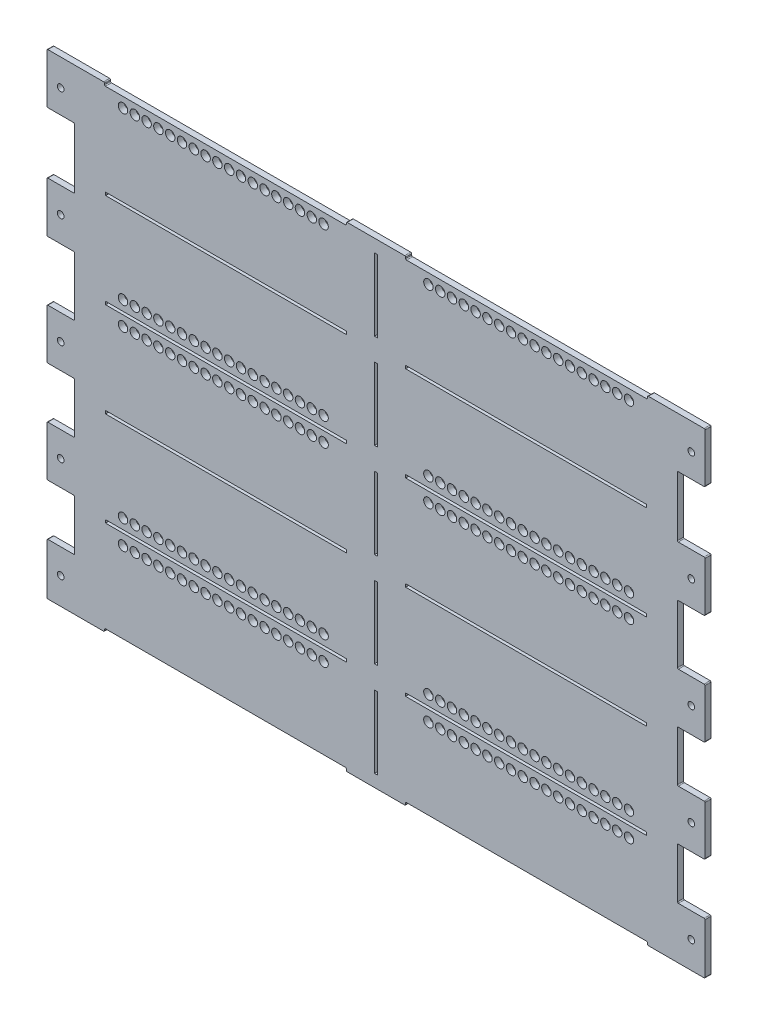
SolidWorks part; units mm, degrees
material "6061-T6 (SS)"
ref_plane "X-Y Datum" through (0, 0, 0) normal (0, 0, 1) x (1, 0, 0)
ref_plane "X-Z Datum" through (0, 0, 0) normal (0, 1, 0) x (1, 0, 0)
ref_plane "Y-Z Datum" through (0, 0, 0) normal (1, 0, 0) x (0, 0, -1)
sketch "Sketch1" plane through (0, 0, 0) normal (0, 0, 1) x (1, 0, 0)
  line L0 (-1.27, -1.27) -> (-1.27, 95.3084)
  line L1 (0, 0) -> (310.8274, 0)
  line L2 (0, 0) -> (0, 94.0384)
  line L3 (0, 94.0384) -> (310.8274, 94.0384)
  line L4 (310.8274, 0) -> (310.8274, 94.0384)
  line L5 (-1.27, 95.3084) -> (312.0974, 95.3084)
  line L6 (312.0974, -1.27) -> (312.0974, 95.3084)
  line L7 (-1.27, -1.27) -> (312.0974, -1.27)
  line L8 (-2.8575, 96.8959) -> (313.6849, 96.8959)
  line L9 (313.6849, -2.8575) -> (313.6849, 96.8959)
  line L10 (-2.8575, -2.8575) -> (313.6849, -2.8575)
  line L11 (-2.8575, -2.8575) -> (-2.8575, 96.8959)
  line L12 (0, 99.7534) -> (310.8274, 99.7534)
  line L13 (310.8274, 193.7918) -> (310.8274, 99.7534)
  line L14 (0, 193.7918) -> (310.8274, 193.7918)
  line L15 (0, 193.7918) -> (0, 99.7534)
  line L16 (-1.27, 195.0618) -> (312.0974, 195.0618)
  line L17 (312.0974, 195.0618) -> (312.0974, 98.4834)
  line L18 (-1.27, 98.4834) -> (312.0974, 98.4834)
  line L19 (-1.27, 195.0618) -> (-1.27, 98.4834)
  line L20 (-2.8575, 196.6493) -> (-2.8575, 96.8959)
  line L21 (-2.8575, 196.6493) -> (630.2273, 196.6493)
  line L23 (-2.8575, 296.4028) -> (630.2273, 296.4028)
  line L24 (-1.27, 198.2368) -> (-1.27, 294.8153)
  line L25 (-1.27, 294.8153) -> (312.0974, 294.8153)
  line L26 (312.0974, 198.2368) -> (312.0974, 294.8153)
  line L27 (-1.27, 198.2368) -> (312.0974, 198.2368)
  line L28 (0, 199.5068) -> (0, 293.5453)
  line L29 (0, 199.5068) -> (310.8274, 199.5068)
  line L30 (310.8274, 199.5068) -> (310.8274, 293.5453)
  line L31 (0, 293.5453) -> (310.8274, 293.5453)
  line L33 (313.6849, 96.8959) -> (313.6849, 196.6493)
  line L34 (-2.8575, 396.1562) -> (630.2273, 396.1562)
  line L35 (-1.27, 394.5687) -> (312.0974, 394.5687)
  line L36 (312.0974, 394.5687) -> (312.0974, 297.9903)
  line L37 (-1.27, 297.9903) -> (312.0974, 297.9903)
  line L38 (-1.27, 394.5687) -> (-1.27, 297.9903)
  line L39 (0, 393.2987) -> (310.8274, 393.2987)
  line L40 (310.8274, 393.2987) -> (310.8274, 299.2603)
  line L41 (0, 299.2603) -> (310.8274, 299.2603)
  line L42 (0, 393.2987) -> (0, 299.2603)
  line L43 (-2.8575, 296.4028) -> (-2.8575, 196.6493)
  line L44 (-2.8575, 495.9096) -> (-2.8575, 296.4028)
  line L45 (313.6849, 495.9096) -> (313.6849, 296.4028)
  line L46 (313.6849, 196.6493) -> (313.6849, 296.4028)
  line L47 (-2.8575, 495.9096) -> (630.2273, 495.9096)
  line L48 (-1.27, 397.7437) -> (-1.27, 494.3221)
  line L49 (-1.27, 494.3221) -> (312.0974, 494.3221)
  line L50 (312.0974, 397.7437) -> (312.0974, 494.3221)
  line L51 (-1.27, 397.7437) -> (312.0974, 397.7437)
  line L52 (0, 399.0137) -> (0, 493.0521)
  line L53 (0, 493.0521) -> (310.8274, 493.0521)
  line L54 (310.8274, 399.0137) -> (310.8274, 493.0521)
  line L55 (0, 399.0137) -> (310.8274, 399.0137)
  line L56 (313.6849, 595.663) -> (313.6849, 495.9096) construction
  line L57 (628.6398, 397.7437) -> (315.2724, 397.7437)
  line L58 (315.2724, 397.7437) -> (315.2724, 494.3221)
  line L59 (628.6398, 494.3221) -> (315.2724, 494.3221)
  line L60 (628.6398, 397.7437) -> (628.6398, 494.3221)
  line L61 (627.3698, 399.0137) -> (316.5424, 399.0137)
  line L62 (316.5424, 399.0137) -> (316.5424, 493.0521)
  line L63 (627.3698, 493.0521) -> (316.5424, 493.0521)
  line L64 (627.3698, 399.0137) -> (627.3698, 493.0521)
  line L65 (630.2273, 495.9096) -> (630.2273, 296.4028)
  line L66 (628.6398, 394.5687) -> (628.6398, 297.9903)
  line L67 (628.6398, 297.9903) -> (315.2724, 297.9903)
  line L68 (315.2724, 394.5687) -> (315.2724, 297.9903)
  line L69 (628.6398, 394.5687) -> (315.2724, 394.5687)
  line L70 (627.3698, 393.2987) -> (627.3698, 299.2603)
  line L71 (627.3698, 299.2603) -> (316.5424, 299.2603)
  line L72 (316.5424, 393.2987) -> (316.5424, 299.2603)
  line L73 (627.3698, 393.2987) -> (316.5424, 393.2987)
  line L74 (630.2273, 296.4028) -> (630.2273, 196.6493)
  line L75 (628.6398, 198.2368) -> (315.2724, 198.2368)
  line L76 (315.2724, 198.2368) -> (315.2724, 294.8153)
  line L77 (628.6398, 294.8153) -> (315.2724, 294.8153)
  line L78 (628.6398, 198.2368) -> (628.6398, 294.8153)
  line L79 (627.3698, 199.5068) -> (316.5424, 199.5068)
  line L80 (316.5424, 199.5068) -> (316.5424, 293.5453)
  line L81 (627.3698, 293.5453) -> (316.5424, 293.5453)
  line L82 (627.3698, 199.5068) -> (627.3698, 293.5453)
  line L83 (630.2273, 196.6493) -> (630.2273, 96.8959)
  line L84 (628.6398, 195.0618) -> (628.6398, 98.4834)
  line L85 (628.6398, 98.4834) -> (315.2724, 98.4834)
  line L86 (315.2724, 195.0618) -> (315.2724, 98.4834)
  line L87 (628.6398, 195.0618) -> (315.2724, 195.0618)
  line L88 (627.3698, 193.7918) -> (627.3698, 99.7534)
  line L89 (627.3698, 193.7918) -> (316.5424, 193.7918)
  line L90 (316.5424, 193.7918) -> (316.5424, 99.7534)
  line L91 (627.3698, 99.7534) -> (316.5424, 99.7534)
  line L92 (630.2273, -2.8575) -> (630.2273, 96.8959)
  line L93 (630.2273, -2.8575) -> (313.6849, -2.8575)
  line L94 (313.6849, -2.8575) -> (313.6849, 96.8959)
  line L95 (630.2273, 96.8959) -> (313.6849, 96.8959)
  line L96 (628.6398, -1.27) -> (315.2724, -1.27)
  line L97 (315.2724, -1.27) -> (315.2724, 95.3084)
  line L98 (628.6398, 95.3084) -> (315.2724, 95.3084)
  line L99 (628.6398, -1.27) -> (628.6398, 95.3084)
  line L100 (627.3698, 94.0384) -> (316.5424, 94.0384)
  line L101 (316.5424, 0) -> (316.5424, 94.0384)
  line L102 (627.3698, 0) -> (316.5424, 0)
  line L103 (627.3698, 0) -> (627.3698, 94.0384)
  point P56 (313.6849, 396.1562)
  dimension "D1" = 310.8274
  dimension "D2" = 94.0384
  dimension "D3" = 1.27
  dimension "D4" = 1.5875
sketch "Sketch2" plane through (0, 0, 0) normal (0, 0, 1) x (1, 0, 0)
  line L0 (0, 47.0192) -> (310.8274, 47.0192) construction
  line L1 (-1.27, -1.27) -> (628.6398, -1.27)
  line L2 (-1.27, -1.27) -> (-1.27, 494.3221)
  line L3 (-1.27, 494.3221) -> (628.6398, 494.3221)
  line L4 (628.6398, -1.27) -> (628.6398, 494.3221)
  line L5 (0, 0) -> (0, 94.0384) construction
  line L6 (310.8274, 0) -> (310.8274, 94.0384) construction
  line L7 (155.4137, 47.0192) -> (155.4137, 163.8162) construction
  line L8 (-2.8575, 96.8959) -> (313.6849, 96.8959) construction
  line L9 (28.4137, 95.3084) -> (282.4137, 95.3084)
  line L10 (28.4137, 95.3084) -> (28.4137, 98.4834)
  line L11 (28.4137, 98.4834) -> (282.4137, 98.4834)
  line L12 (282.4137, 95.3084) -> (282.4137, 98.4834)
  line L13 (28.4137, 95.3084) -> (282.4137, 98.4834) construction
  line L14 (28.4137, 98.4834) -> (282.4137, 95.3084) construction
  line L15 (-1.27, 98.4834) -> (312.0974, 98.4834) construction
  line L16 (-2.8575, 196.6493) -> (630.2273, 196.6493) construction
  line L17 (28.4137, 195.0618) -> (282.4137, 195.0618)
  line L18 (28.4137, 195.0618) -> (28.4137, 198.2368)
  line L19 (28.4137, 198.2368) -> (282.4137, 198.2368)
  line L20 (282.4137, 195.0618) -> (282.4137, 198.2368)
  line L21 (28.4137, 195.0618) -> (282.4137, 198.2368) construction
  line L22 (28.4137, 198.2368) -> (282.4137, 195.0618) construction
  line L23 (-1.27, 198.2368) -> (312.0974, 198.2368) construction
  line L24 (315.2724, -1.27) -> (315.2724, 95.3084) construction
  line L25 (-2.8575, 296.4028) -> (630.2273, 296.4028) construction
  line L26 (28.4137, 294.8153) -> (282.4137, 294.8153)
  line L27 (28.4137, 294.8153) -> (28.4137, 297.9903)
  line L28 (28.4137, 297.9903) -> (282.4137, 297.9903)
  line L29 (282.4137, 294.8153) -> (282.4137, 297.9903)
  line L30 (28.4137, 294.8153) -> (282.4137, 297.9903) construction
  line L31 (28.4137, 297.9903) -> (282.4137, 294.8153) construction
  line L32 (-1.27, 297.9903) -> (312.0974, 297.9903) construction
  line L33 (-2.8575, 396.1562) -> (630.2273, 396.1562) construction
  line L34 (28.4137, 394.5687) -> (282.4137, 394.5687)
  line L35 (28.4137, 394.5687) -> (28.4137, 397.7437)
  line L36 (28.4137, 397.7437) -> (282.4137, 397.7437)
  line L37 (282.4137, 394.5687) -> (282.4137, 397.7437)
  line L38 (28.4137, 394.5687) -> (282.4137, 397.7437) construction
  line L39 (28.4137, 397.7437) -> (282.4137, 394.5687) construction
  line L40 (-1.27, 397.7437) -> (312.0974, 397.7437) construction
  line L41 (313.6849, 604.3732) -> (313.6849, -52.4712) construction
  line L42 (598.9561, 98.4834) -> (344.9561, 98.4834)
  line L43 (344.9561, 95.3084) -> (344.9561, 98.4834)
  line L44 (598.9561, 95.3084) -> (344.9561, 95.3084)
  line L45 (598.9561, 95.3084) -> (598.9561, 98.4834)
  line L46 (598.9561, 198.2368) -> (344.9561, 198.2368)
  line L47 (344.9561, 195.0618) -> (344.9561, 198.2368)
  line L48 (598.9561, 195.0618) -> (344.9561, 195.0618)
  line L49 (598.9561, 195.0618) -> (598.9561, 198.2368)
  line L50 (598.9561, 397.7437) -> (344.9561, 397.7437)
  line L51 (344.9561, 394.5687) -> (344.9561, 397.7437)
  line L52 (598.9561, 394.5687) -> (344.9561, 394.5687)
  line L53 (598.9561, 394.5687) -> (598.9561, 397.7437)
  line L54 (598.9561, 297.9903) -> (344.9561, 297.9903)
  line L55 (344.9561, 294.8153) -> (344.9561, 297.9903)
  line L56 (598.9561, 294.8153) -> (344.9561, 294.8153)
  line L57 (598.9561, 294.8153) -> (598.9561, 297.9903)
  line L58 (312.0974, 8.5255) -> (315.2724, 8.5255)
  line L59 (312.0974, 8.5255) -> (312.0974, 84.7255)
  line L60 (312.0974, 84.7255) -> (315.2724, 84.7255)
  line L61 (315.2724, 8.5255) -> (315.2724, 84.7255)
  line L62 (312.0974, 8.5255) -> (315.2724, 84.7255) construction
  line L63 (312.0974, 84.7255) -> (315.2724, 8.5255) construction
  line L64 (310.8274, 193.7918) -> (310.8274, 99.7534) construction
  line L65 (310.8274, 146.7726) -> (337.6409, 146.7726) construction
  line L66 (315.2724, 195.0618) -> (315.2724, 98.4834) construction
  line L67 (312.0974, 108.6726) -> (315.2724, 108.6726)
  line L68 (312.0974, 108.6726) -> (312.0974, 184.8726)
  line L69 (312.0974, 184.8726) -> (315.2724, 184.8726)
  line L70 (315.2724, 108.6726) -> (315.2724, 184.8726)
  line L71 (312.0974, 108.6726) -> (315.2724, 184.8726) construction
  line L72 (312.0974, 184.8726) -> (315.2724, 108.6726) construction
  line L73 (310.8274, 293.5453) -> (310.8274, 199.5068) construction
  line L74 (310.8274, 246.5261) -> (343.3258, 246.5261) construction
  line L75 (315.2724, 198.2368) -> (315.2724, 294.8153) construction
  line L76 (312.0974, 208.4261) -> (315.2724, 208.4261)
  line L77 (312.0974, 208.4261) -> (312.0974, 284.6261)
  line L78 (312.0974, 284.6261) -> (315.2724, 284.6261)
  line L79 (315.2724, 208.4261) -> (315.2724, 284.6261)
  line L80 (312.0974, 208.4261) -> (315.2724, 284.6261) construction
  line L81 (312.0974, 284.6261) -> (315.2724, 208.4261) construction
  line L82 (310.8274, 299.2603) -> (310.8274, 393.2987) construction
  line L83 (310.8274, 493.0521) -> (310.8274, 399.0137) construction
  line L84 (310.8274, 346.2795) -> (351.536, 346.2795) construction
  line L85 (310.8274, 446.0329) -> (345.4409, 446.0329) construction
  line L86 (315.2724, 394.5687) -> (315.2724, 297.9903) construction
  line L87 (312.0974, 308.1795) -> (315.2724, 308.1795)
  line L88 (312.0974, 308.1795) -> (312.0974, 384.3795)
  line L89 (312.0974, 384.3795) -> (315.2724, 384.3795)
  line L90 (315.2724, 308.1795) -> (315.2724, 384.3795)
  line L91 (312.0974, 308.1795) -> (315.2724, 384.3795) construction
  line L92 (312.0974, 384.3795) -> (315.2724, 308.1795) construction
  line L93 (315.2724, 397.7437) -> (315.2724, 494.3221) construction
  line L94 (312.0974, 407.9329) -> (315.2724, 407.9329)
  line L95 (312.0974, 407.9329) -> (312.0974, 484.1329)
  line L96 (312.0974, 484.1329) -> (315.2724, 484.1329)
  line L97 (315.2724, 407.9329) -> (315.2724, 484.1329)
  line L98 (312.0974, 407.9329) -> (315.2724, 484.1329) construction
  line L99 (312.0974, 484.1329) -> (315.2724, 407.9329) construction
  point P13 (155.4137, 96.8959)
  point P23 (155.4137, 196.6493)
  point P32 (155.4137, 296.4028)
  point P41 (155.4137, 396.1562)
  point P52 (313.6849, 46.6255)
  point P80 (313.6849, 146.7726)
  point P93 (313.6849, 246.526)
  point P114 (313.6849, 346.2795)
  point P122 (313.6849, 446.0329)
  dimension "D1" = 254
  dimension "D2" = 254
  dimension "D3" = 254
  dimension "D4" = 254
  dimension "D5" = 76.2
  dimension "D6" = 76.2
  dimension "D7" = 3.175
  dimension "D8" = 99.7534
  dimension "D9" = 76.2
  dimension "D10" = 99.7534
  dimension "D11" = 99.7534
  dimension "D12" = 99.7534
  dimension "D13" = 76.2
  dimension "D14" = 76.2
extrude "Boss-Extrude1" add sketch "Sketch2" along normal blind 6.35
sketch "Sketch4" plane through (0, 0, 6.35) normal (0, 0, 1) x (1, 0, 0)
  line L0 (313.6849, 484.1329) -> (313.6849, 506.6663) construction
  line L1 (-1.27, -1.27) -> (27.315, -1.27)
  line L2 (-1.27, -1.27) -> (-1.27, -4.445)
  line L3 (-1.27, -4.445) -> (27.315, -4.445)
  line L4 (628.6398, -1.27) -> (628.6398, -4.445)
  line L6 (27.315, -1.27) -> (27.315, -4.445)
  line L8 (282.4137, -1.27) -> (282.4137, -4.445)
  line L9 (600.0548, -1.27) -> (628.6398, -1.27)
  line L11 (344.9561, -1.27) -> (344.9561, -4.445)
  line L13 (600.0548, -1.27) -> (600.0548, -4.445)
  line L14 (600.0548, -4.445) -> (628.6398, -4.445)
  line L15 (282.4137, -1.27) -> (344.9561, -1.27)
  line L16 (282.4137, -4.445) -> (344.9561, -4.445)
  line L17 (-1.27, 246.526) -> (668.9088, 246.526) construction
  line L18 (-1.27, 494.3221) -> (-1.27, -1.27) construction
  line L19 (600.0548, 494.3221) -> (628.6398, 494.3221)
  line L20 (600.0548, 494.3221) -> (600.0548, 497.4971)
  line L21 (600.0548, 497.4971) -> (628.6398, 497.4971)
  line L22 (628.6398, 494.3221) -> (628.6398, 497.4971)
  line L23 (282.4137, 494.3221) -> (344.9561, 494.3221)
  line L24 (344.9561, 494.3221) -> (344.9561, 497.4971)
  line L25 (282.4137, 497.4971) -> (344.9561, 497.4971)
  line L26 (282.4137, 494.3221) -> (282.4137, 497.4971)
  line L27 (-1.27, 494.3221) -> (27.315, 494.3221)
  line L28 (-1.27, 494.3221) -> (-1.27, 497.4971)
  line L29 (-1.27, 497.4971) -> (27.315, 497.4971)
  line L30 (27.315, 494.3221) -> (27.315, 497.4971)
extrude "Boss-Extrude2" add sketch "Sketch4" against normal through all contours L3 L0 L1 L8 L6 L2 | L0 L3 L4 L1 L13 L11 | L13 L14 L4 L9 | L26 L23 L24 L25 | L19 L22 L21 L20 | L8 L16 L11 L15 | L4 L14 L13 L9 | L29 L30 L27 L28 region at (13.0225, -2.8575, 6.35) region at (614.3473, -2.8575, 6.35) region at (614.3473, 495.9096, 6.35) region at (313.6849, 495.9096, 6.35)
sketch "Sketch5" plane through (0, 0, 6.35) normal (0, 0, 1) x (1, 0, 0)
  line L0 (313.6849, 646.2482) -> (313.6849, -137.2183) construction
  line L9 (628.6398, 526.4531) -> (469.3361, 526.4531) construction
  line L18 (469.3361, 510.1236) -> (469.3361, 526.4531) construction
  line L19 (-1.27, 494.3221) -> (628.6398, 494.3221) construction
  line L20 (-1.27, 494.3221) -> (-1.27, 497.4971) construction
  line L21 (158.0337, 510.1236) -> (469.3361, 510.1236) construction
  line L22 (628.6398, 494.3221) -> (628.6398, 497.4971) construction
  line L24 (-1.27, 497.4971) -> (-1.27, 526.4531) construction
  line L25 (-1.27, 526.4531) -> (158.0337, 526.4531) construction
  line L26 (158.0337, 510.1236) -> (158.0337, 526.4531) construction
  line L28 (628.6398, 497.4971) -> (628.6398, 526.4531) construction
  line L29 (-1.27, 244.9386) -> (684.2814, 244.9386) construction
  line L30 (-33.401, 494.3221) -> (-33.401, 497.4971)
  line L41 (628.6398, 494.3221) -> (628.6398, -4.445)
  line L43 (660.7708, 494.3221) -> (660.7708, -4.445)
  line L44 (628.6398, -4.445) -> (660.7708, -4.445)
  line L45 (-1.27, -4.445) -> (-33.401, -4.445)
  line L46 (-33.401, 494.3221) -> (-33.401, -4.445)
  line L48 (-1.27, 494.3221) -> (-1.27, -4.445)
  line L49 (-33.401, 497.4971) -> (-1.27, 497.4971)
  line L50 (-1.27, 497.4971) -> (-1.27, 494.3221)
  line L51 (628.6398, 497.4971) -> (660.7708, 497.4971)
  line L52 (660.7708, 497.4971) -> (660.7708, 494.3221)
  line L53 (628.6398, 497.4971) -> (628.6398, 494.3221)
extrude "Boss-Extrude3" add sketch "Sketch5" against normal through all
sketch "Sketch6" plane through (0, 0, 6.35) normal (0, 0, 1) x (1, 0, 0)
  line L0 (-33.401, 497.4971) -> (-33.401, -4.445) construction
  line L1 (-18.923, 237.4868) -> (-18.923, 23.73) construction
  line L2 (-58.003, 491.1471) -> (-58.003, 0) construction
  line L4 (-33.401, -4.445) -> (27.315, -4.445) construction
  line L5 (-18.923, 486.1471) -> (-18.923, 469.3221) construction
  line L6 (-18.923, 469.3221) -> (-18.923, 237.4868) construction
  line L7 (313.6849, 494.3221) -> (313.6849, 517.9624) construction
  line L8 (-33.401, 497.4971) -> (27.315, 497.4971) construction
  circle A0 centre (-18.923, 23.73) radius 7.1006 construction
  circle A1 centre (-18.923, 469.3221) radius 7.1006 construction
  circle A2 centre (-18.923, 237.4868) radius 7.1006 construction
  circle A3 centre (-18.923, 130.6084) radius 7.1006 construction
  circle A4 centre (-18.923, 353.4045) radius 7.1006 construction
  point P17 (-18.923, 469.3221)
  point P18 (-18.923, 23.73)
  point P21 (-18.923, 237.4868)
  point P22 (-18.923, 130.6084)
  point P25 (-18.923, 353.4045)
  point P26 (646.2928, 23.73)
  point P27 (646.2928, 130.6084)
  point P28 (646.2928, 237.4868)
  point P30 (646.2928, 353.4045)
  point P31 (646.2928, 469.3221)
  dimension "D1" = 14.478
  dimension "D2" = 28.175
  dimension "D3" = 28.175
hole_wizard "M6 Clearance Hole1" positions "Sketch11" profile "Sketch10" hole size "M6" standard "ANSI Metric" end condition through all
sketch "Sketch11" plane through (0, 0, 6.35) normal (0, 0, 1) x (1, 0, 0)
  line L0 (-18.923, 237.4868) -> (-18.923, 23.73) construction
  point P0 (-18.923, 469.3221)
  point P3 (-18.923, 353.4045)
  point P6 (-18.923, 237.4868)
  point P9 (-18.923, 130.6084)
  point P13 (-18.923, 23.73)
  point P16 (646.2928, 23.73)
  point P19 (646.2928, 130.6084)
  point P22 (646.2928, 237.4868)
  point P25 (646.2928, 353.4045)
  point P28 (646.2928, 469.3221)
sketch "Sketch10" plane through (-18.923, 469.3221, 6.35) normal (1, 0, 0) x (0, -1, 0)
  line L0 (0, 0) -> (0, 6.35)
  line L1 (0, 6.35) -> (3.5, 6.35)
  line L2 (3.5, 6.35) -> (3.5, 0)
  line L5 (3.5, 0) -> (0, 0)
  line L11 (0, -6.35) -> (0, 107.95) construction
  dimension "Thru Hole Dia." = 7
  dimension "Thru Hole Depth" = 6.35
sketch "Sketch13" plane through (0, 0, 6.35) normal (0, 0, 1) x (1, 0, 0)
  line L0 (-33.401, 444.3971) -> (-4.3178, 444.3971)
  line L1 (-33.401, 444.3971) -> (-33.401, 380.1105)
  line L2 (-33.401, 380.1105) -> (-4.3178, 380.1105)
  line L3 (-4.3178, 444.3971) -> (-4.3178, 380.1105)
  line L4 (-33.401, 326.6985) -> (-4.3178, 326.6985)
  line L5 (-33.401, 326.6985) -> (-33.401, 263.9908)
  line L6 (-33.401, 263.9908) -> (-4.3178, 263.9908)
  line L7 (-4.3178, 326.6985) -> (-4.3178, 263.9908)
  line L8 (-33.401, 210.9829) -> (-4.3178, 210.9829)
  line L9 (-33.401, 210.9829) -> (-33.401, 157.1261)
  line L10 (-33.401, 157.1261) -> (-4.3178, 157.1261)
  line L11 (-4.3178, 210.9829) -> (-4.3178, 157.1261)
  line L12 (-33.401, 104.0907) -> (-4.3178, 104.0907)
  line L13 (-33.401, 104.0907) -> (-33.401, 50.0595)
  line L14 (-33.401, 50.0595) -> (-4.3178, 50.0595)
  line L15 (-4.3178, 104.0907) -> (-4.3178, 50.0595)
  line L32 (-33.5282, 492.6971) -> (660.7708, 492.6971) construction
  line L33 (-33.5282, 492.6971) -> (-33.5282, -1.3734) construction
  line L34 (-33.5282, -1.3734) -> (660.7708, -1.3734) construction
  line L36 (313.6849, 84.7255) -> (313.6849, 116.6988) construction
  line L37 (-33.401, 497.4971) -> (-4.445, 497.4971) construction
  line L38 (-33.401, 497.4971) -> (-33.401, 418.9959) construction
  line L39 (-33.401, 418.9959) -> (-4.445, 418.9959) construction
  line L40 (-4.445, 497.4971) -> (-4.445, 418.9959) construction
  line L41 (-4.3178, 326.6985) -> (-33.5282, 326.6985) construction
  line L42 (-4.3178, 326.6985) -> (-4.3178, 380.1105) construction
  line L43 (-4.3178, 380.1105) -> (-33.5282, 380.1105) construction
  line L44 (-33.5282, 326.6985) -> (-33.5282, 380.1105) construction
  line L45 (-4.3178, 326.6985) -> (-33.5282, 380.1105) construction
  line L46 (-4.3178, 380.1105) -> (-33.5282, 326.6985) construction
  line L47 (-33.5282, 210.9829) -> (-4.3178, 210.9829) construction
  line L48 (-33.5282, 210.9829) -> (-33.5282, 263.9908) construction
  line L49 (-33.5282, 263.9908) -> (-4.3178, 263.9908) construction
  line L50 (-4.3178, 210.9829) -> (-4.3178, 263.9908) construction
  line L51 (-33.5282, 210.9829) -> (-4.3178, 263.9908) construction
  line L52 (-33.5282, 263.9908) -> (-4.3178, 210.9829) construction
  line L53 (-33.5282, 104.0907) -> (-4.3178, 104.0907) construction
  line L54 (-33.5282, 104.0907) -> (-33.5282, 157.1261) construction
  line L55 (-33.5282, 157.1261) -> (-4.3178, 157.1261) construction
  line L56 (-4.3178, 104.0907) -> (-4.3178, 157.1261) construction
  line L57 (-33.5282, 104.0907) -> (-4.3178, 157.1261) construction
  line L58 (-33.5282, 157.1261) -> (-4.3178, 104.0907) construction
  line L59 (-33.5282, -2.5995) -> (-4.3178, -2.5995) construction
  line L60 (-33.5282, -2.5995) -> (-33.5282, 50.0595) construction
  line L61 (-33.5282, 50.0595) -> (-4.3178, 50.0595) construction
  line L62 (-4.3178, -2.5995) -> (-4.3178, 50.0595) construction
  line L63 (-33.5282, -2.5995) -> (-4.3178, 50.0595) construction
  line L64 (-33.5282, 50.0595) -> (-4.3178, -2.5995) construction
  line L66 (660.7708, 104.0907) -> (660.7708, 50.0595)
  line L67 (660.7708, 50.0595) -> (631.6876, 50.0595)
  line L68 (631.6876, 104.0907) -> (631.6876, 50.0595)
  line L69 (660.7708, 104.0907) -> (631.6876, 104.0907)
  line L70 (660.7708, 210.9829) -> (660.7708, 157.1261)
  line L71 (660.7708, 157.1261) -> (631.6876, 157.1261)
  line L72 (631.6876, 210.9829) -> (631.6876, 157.1261)
  line L73 (660.7708, 210.9829) -> (631.6876, 210.9829)
  line L74 (660.7708, 326.6985) -> (660.7708, 263.9908)
  line L75 (660.7708, 263.9908) -> (631.6876, 263.9908)
  line L76 (631.6876, 326.6985) -> (631.6876, 263.9908)
  line L77 (660.7708, 326.6985) -> (631.6876, 326.6985)
  line L78 (660.7708, 444.3971) -> (660.7708, 380.1105)
  line L79 (660.7708, 380.1105) -> (631.6876, 380.1105)
  line L80 (631.6876, 444.3971) -> (631.6876, 380.1105)
  line L81 (660.7708, 444.3971) -> (631.6876, 444.3971)
  point P1 (-18.923, 237.4868)
  point P5 (-18.923, 130.6084)
  point P9 (-18.923, 23.73)
  point P41 (-18.923, 353.4045)
extrude "Cut-Extrude1" cut sketch "Sketch13" against normal through all
sketch "Sketch15" plane through (0, 0, 0) normal (0, 0, 1) x (1, 0, 0)
  line L0 (28.4137, 397.7437) -> (282.4137, 397.7437) construction
  line L1 (28.4137, 394.5687) -> (279.5273, 394.5687) construction
  line L2 (28.4137, 394.5687) -> (282.4137, 394.5687) construction
  line L7 (-1.27, 491.1471) -> (628.6398, 491.1471) construction
  line L8 (-1.27, 491.1471) -> (-1.27, 0.1766) construction
  line L9 (-1.27, 0.1766) -> (628.6398, 0.1766) construction
  line L10 (628.6398, 491.1471) -> (628.6398, 0.1766) construction
  line L11 (28.4137, 198.2368) -> (282.4137, 198.2368) construction
  line L12 (282.4137, 195.0618) -> (28.4137, 195.0618) construction
  line L13 (27.315, -1.27) -> (282.4137, -1.27) construction
  line L14 (313.6849, 484.1329) -> (313.6849, 511.0054) construction
  line L15 (312.0974, 446.0329) -> (-60.7128, 446.0329) construction
  line L16 (312.0974, 484.1329) -> (312.0974, 407.9329) construction
  line L17 (312.0974, 346.2795) -> (183.7106, 346.2795) construction
  line L18 (312.0974, 46.6255) -> (242.3736, 46.6255) construction
  line L19 (312.0974, 246.5261) -> (190.4752, 246.5261) construction
  line L21 (312.0974, 146.7726) -> (233.4946, 146.7726) construction
  line L22 (312.0974, 184.8726) -> (312.0974, 108.6726) construction
  circle A306 centre (580.5653, 483.6541) radius 5
  circle A307 centre (568.1193, 483.6541) radius 5
  circle A308 centre (555.6733, 483.6541) radius 5
  circle A309 centre (543.2273, 483.6541) radius 5
  circle A310 centre (530.7813, 483.6541) radius 5
  circle A311 centre (518.3353, 483.6541) radius 5
  circle A312 centre (505.8893, 483.6541) radius 5
  circle A313 centre (493.4433, 483.6541) radius 5
  circle A314 centre (480.9973, 483.6541) radius 5
  circle A315 centre (468.5513, 483.6541) radius 5
  circle A316 centre (456.1053, 483.6541) radius 5
  circle A317 centre (443.6593, 483.6541) radius 5
  circle A318 centre (431.2133, 483.6541) radius 5
  circle A319 centre (418.7673, 483.6541) radius 5
  circle A320 centre (406.3213, 483.6541) radius 5
  circle A321 centre (393.8753, 483.6541) radius 5
  circle A322 centre (381.4293, 483.6541) radius 5
  circle A323 centre (368.9833, 483.6541) radius 5
  circle A324 centre (258.3866, 483.6541) radius 5
  circle A325 centre (245.9406, 483.6541) radius 5
  circle A326 centre (233.4946, 483.6541) radius 5
  circle A327 centre (221.0486, 483.6541) radius 5
  circle A328 centre (208.6026, 483.6541) radius 5
  circle A329 centre (196.1566, 483.6541) radius 5
  circle A330 centre (183.7106, 483.6541) radius 5
  circle A331 centre (171.2646, 483.6541) radius 5
  circle A332 centre (158.8186, 483.6541) radius 5
  circle A333 centre (146.3726, 483.6541) radius 5
  circle A334 centre (133.9266, 483.6541) radius 5
  circle A335 centre (121.4806, 483.6541) radius 5
  circle A336 centre (109.0346, 483.6541) radius 5
  circle A337 centre (96.5886, 483.6541) radius 5
  circle A338 centre (84.1426, 483.6541) radius 5
  circle A339 centre (71.6966, 483.6541) radius 5
  circle A340 centre (59.2506, 483.6541) radius 5
  circle A341 centre (46.8046, 483.6541) radius 5
  circle A359 centre (580.5653, 308.6583) radius 5
  circle A360 centre (568.1193, 308.6583) radius 5
  circle A361 centre (555.6733, 308.6583) radius 5
  circle A362 centre (543.2273, 308.6583) radius 5
  circle A363 centre (530.7813, 308.6583) radius 5
  circle A364 centre (518.3353, 308.6583) radius 5
  circle A365 centre (505.8893, 308.6583) radius 5
  circle A366 centre (493.4433, 308.6583) radius 5
  circle A367 centre (480.9973, 308.6583) radius 5
  circle A368 centre (468.5513, 308.6583) radius 5
  circle A369 centre (456.1053, 308.6583) radius 5
  circle A370 centre (443.6593, 308.6583) radius 5
  circle A371 centre (431.2133, 308.6583) radius 5
  circle A372 centre (418.7673, 308.6583) radius 5
  circle A373 centre (406.3213, 308.6583) radius 5
  circle A374 centre (393.8753, 308.6583) radius 5
  circle A375 centre (381.4293, 308.6583) radius 5
  circle A376 centre (368.9833, 308.6583) radius 5
  circle A377 centre (258.3866, 308.6583) radius 5
  circle A378 centre (245.9406, 308.6583) radius 5
  circle A379 centre (233.4946, 308.6583) radius 5
  circle A380 centre (221.0486, 308.6583) radius 5
  circle A381 centre (208.6026, 308.6583) radius 5
  circle A382 centre (196.1566, 308.6583) radius 5
  circle A383 centre (183.7106, 308.6583) radius 5
  circle A384 centre (171.2646, 308.6583) radius 5
  circle A385 centre (158.8186, 308.6583) radius 5
  circle A386 centre (146.3726, 308.6583) radius 5
  circle A387 centre (133.9266, 308.6583) radius 5
  circle A388 centre (121.4806, 308.6583) radius 5
  circle A389 centre (109.0346, 308.6583) radius 5
  circle A390 centre (96.5886, 308.6583) radius 5
  circle A391 centre (84.1426, 308.6583) radius 5
  circle A392 centre (71.6966, 308.6583) radius 5
  circle A393 centre (59.2506, 308.6583) radius 5
  circle A394 centre (46.8046, 308.6583) radius 5
  circle A412 centre (580.5653, 284.1473) radius 5
  circle A413 centre (568.1193, 284.1473) radius 5
  circle A414 centre (555.6733, 284.1473) radius 5
  circle A415 centre (543.2273, 284.1473) radius 5
  circle A416 centre (530.7813, 284.1473) radius 5
  circle A417 centre (518.3353, 284.1473) radius 5
  circle A418 centre (505.8893, 284.1473) radius 5
  circle A419 centre (493.4433, 284.1473) radius 5
  circle A420 centre (480.9973, 284.1473) radius 5
  circle A421 centre (468.5513, 284.1473) radius 5
  circle A422 centre (456.1053, 284.1473) radius 5
  circle A423 centre (443.6593, 284.1473) radius 5
  circle A424 centre (431.2133, 284.1473) radius 5
  circle A425 centre (418.7673, 284.1473) radius 5
  circle A426 centre (406.3213, 284.1473) radius 5
  circle A427 centre (393.8753, 284.1473) radius 5
  circle A428 centre (381.4293, 284.1473) radius 5
  circle A429 centre (368.9833, 284.1473) radius 5
  circle A430 centre (258.3866, 284.1473) radius 5
  circle A431 centre (245.9406, 284.1473) radius 5
  circle A432 centre (233.4946, 284.1473) radius 5
  circle A433 centre (221.0486, 284.1473) radius 5
  circle A434 centre (208.6026, 284.1473) radius 5
  circle A435 centre (196.1566, 284.1473) radius 5
  circle A436 centre (183.7106, 284.1473) radius 5
  circle A437 centre (171.2646, 284.1473) radius 5
  circle A438 centre (158.8186, 284.1473) radius 5
  circle A439 centre (146.3726, 284.1473) radius 5
  circle A440 centre (133.9266, 284.1473) radius 5
  circle A441 centre (121.4806, 284.1473) radius 5
  circle A442 centre (109.0346, 284.1473) radius 5
  circle A443 centre (96.5886, 284.1473) radius 5
  circle A444 centre (84.1426, 284.1473) radius 5
  circle A445 centre (71.6966, 284.1473) radius 5
  circle A446 centre (59.2506, 284.1473) radius 5
  circle A447 centre (46.8046, 284.1473) radius 5
  circle A465 centre (580.5653, 109.1514) radius 5
  circle A466 centre (568.1193, 109.1514) radius 5
  circle A467 centre (555.6733, 109.1514) radius 5
  circle A468 centre (543.2273, 109.1514) radius 5
  circle A469 centre (530.7813, 109.1514) radius 5
  circle A470 centre (518.3353, 109.1514) radius 5
  circle A471 centre (505.8893, 109.1514) radius 5
  circle A472 centre (493.4433, 109.1514) radius 5
  circle A473 centre (480.9973, 109.1514) radius 5
  circle A474 centre (468.5513, 109.1514) radius 5
  circle A475 centre (456.1053, 109.1514) radius 5
  circle A476 centre (443.6593, 109.1514) radius 5
  circle A477 centre (431.2133, 109.1514) radius 5
  circle A478 centre (418.7673, 109.1514) radius 5
  circle A479 centre (406.3213, 109.1514) radius 5
  circle A480 centre (393.8753, 109.1514) radius 5
  circle A481 centre (381.4293, 109.1514) radius 5
  circle A482 centre (368.9833, 109.1514) radius 5
  circle A483 centre (258.3866, 109.1514) radius 5
  circle A484 centre (245.9406, 109.1514) radius 5
  circle A485 centre (233.4946, 109.1514) radius 5
  circle A486 centre (221.0486, 109.1514) radius 5
  circle A487 centre (208.6026, 109.1514) radius 5
  circle A488 centre (196.1566, 109.1514) radius 5
  circle A489 centre (183.7106, 109.1514) radius 5
  circle A490 centre (171.2646, 109.1514) radius 5
  circle A491 centre (158.8186, 109.1514) radius 5
  circle A492 centre (146.3726, 109.1514) radius 5
  circle A493 centre (133.9266, 109.1514) radius 5
  circle A494 centre (121.4806, 109.1514) radius 5
  circle A495 centre (109.0346, 109.1514) radius 5
  circle A496 centre (96.5886, 109.1514) radius 5
  circle A497 centre (84.1426, 109.1514) radius 5
  circle A498 centre (71.6966, 109.1514) radius 5
  circle A499 centre (59.2506, 109.1514) radius 5
  circle A500 centre (46.8046, 109.1514) radius 5
  circle A554 centre (580.5653, 83.853) radius 5
  circle A555 centre (568.1193, 83.853) radius 5
  circle A556 centre (555.6733, 83.853) radius 5
  circle A557 centre (543.2273, 83.853) radius 5
  circle A558 centre (530.7813, 83.853) radius 5
  circle A559 centre (518.3353, 83.853) radius 5
  circle A560 centre (505.8893, 83.853) radius 5
  circle A561 centre (493.4433, 83.853) radius 5
  circle A562 centre (480.9973, 83.853) radius 5
  circle A563 centre (468.5513, 83.853) radius 5
  circle A564 centre (456.1053, 83.853) radius 5
  circle A565 centre (443.6593, 83.853) radius 5
  circle A566 centre (431.2133, 83.853) radius 5
  circle A567 centre (418.7673, 83.853) radius 5
  circle A568 centre (406.3213, 83.853) radius 5
  circle A569 centre (393.8753, 83.853) radius 5
  circle A570 centre (381.4293, 83.853) radius 5
  circle A571 centre (368.9833, 83.853) radius 5
  circle A572 centre (258.3866, 83.853) radius 5
  circle A573 centre (245.9406, 83.853) radius 5
  circle A574 centre (233.4946, 83.853) radius 5
  circle A575 centre (221.0486, 83.853) radius 5
  circle A576 centre (208.6026, 83.853) radius 5
  circle A577 centre (196.1566, 83.853) radius 5
  circle A578 centre (183.7106, 83.853) radius 5
  circle A579 centre (171.2646, 83.853) radius 5
  circle A580 centre (158.8186, 83.853) radius 5
  circle A581 centre (146.3726, 83.853) radius 5
  circle A582 centre (133.9266, 83.853) radius 5
  circle A583 centre (121.4806, 83.853) radius 5
  circle A584 centre (109.0346, 83.853) radius 5
  circle A585 centre (96.5886, 83.853) radius 5
  circle A586 centre (84.1426, 83.853) radius 5
  circle A587 centre (71.6966, 83.853) radius 5
  circle A588 centre (59.2506, 83.853) radius 5
  circle A589 centre (46.8046, 83.853) radius 5
  circle A590 centre (580.5653, 83.853) radius 5
  circle A591 centre (568.1193, 83.853) radius 5
  circle A592 centre (555.6733, 83.853) radius 5
  circle A593 centre (543.2273, 83.853) radius 5
  circle A594 centre (530.7813, 83.853) radius 5
  circle A595 centre (518.3353, 83.853) radius 5
  circle A596 centre (505.8893, 83.853) radius 5
  circle A597 centre (493.4433, 83.853) radius 5
  circle A598 centre (480.9973, 83.853) radius 5
  circle A599 centre (468.5513, 83.853) radius 5
  circle A600 centre (456.1053, 83.853) radius 5
  circle A601 centre (443.6593, 83.853) radius 5
  circle A602 centre (431.2133, 83.853) radius 5
  circle A603 centre (418.7673, 83.853) radius 5
  circle A604 centre (406.3213, 83.853) radius 5
  circle A605 centre (393.8753, 83.853) radius 5
  circle A606 centre (381.4293, 83.853) radius 5
  circle A607 centre (368.9833, 83.853) radius 5
  circle A608 centre (258.3866, 83.853) radius 5
  circle A609 centre (245.9406, 83.853) radius 5
  circle A610 centre (233.4946, 83.853) radius 5
  circle A611 centre (221.0486, 83.853) radius 5
  circle A612 centre (208.6026, 83.853) radius 5
  circle A613 centre (196.1566, 83.853) radius 5
  circle A614 centre (183.7106, 83.853) radius 5
  circle A615 centre (171.2646, 83.853) radius 5
  circle A616 centre (158.8186, 83.853) radius 5
  circle A617 centre (146.3726, 83.853) radius 5
  circle A618 centre (133.9266, 83.853) radius 5
  circle A619 centre (121.4806, 83.853) radius 5
  circle A620 centre (109.0346, 83.853) radius 5
  circle A621 centre (96.5886, 83.853) radius 5
  circle A622 centre (84.1426, 83.853) radius 5
  circle A623 centre (71.6966, 83.853) radius 5
  circle A624 centre (59.2506, 83.853) radius 5
  circle A625 centre (46.8046, 83.853) radius 5
extrude "Cut-Extrude5" cut sketch "Sketch15" along normal through all
fillet "Fillet1" radius 1 52 edges at (27.315, 497.4971, 3.175) (27.315, 494.3221, 3.175) (282.4137, 494.3221, 3.175) (282.4137, 497.4971, 3.175) (344.9561, 497.4971, 3.175) (344.9561, 494.3221, 3.175) (600.0548, 494.3221, 3.175) (600.0548, 497.4971, 3.175) (660.7708, 497.4971, 3.175) (660.7708, -4.445, 3.175) (600.0548, -4.445, 3.175) (600.0548, -1.27, 3.175) (344.9561, -1.27, 3.175) (344.9561, -4.445, 3.175) (282.4137, -4.445, 3.175) (282.4137, -1.27, 3.175) (27.315, -1.27, 3.175) (27.315, -4.445, 3.175) (-33.401, -4.445, 3.175) (-33.401, 50.0595, 3.175) (-4.3178, 50.0595, 3.175) (-4.3178, 104.0907, 3.175) (-33.401, 104.0907, 3.175) (-33.401, 157.1261, 3.175) (-4.3178, 157.1261, 3.175) (-4.3178, 210.9829, 3.175) (-33.401, 210.9829, 3.175) (-33.401, 263.9908, 3.175) (-4.3178, 263.9908, 3.175) (-4.3178, 326.6985, 3.175) (-33.401, 326.6985, 3.175) (-33.401, 380.1105, 3.175) (-4.3178, 380.1105, 3.175) (-33.401, 444.3971, 3.175) (-4.3178, 444.3971, 3.175) (-33.401, 497.4971, 3.175) (631.6876, 50.0595, 3.175) (660.7708, 50.0595, 3.175) (631.6876, 104.0907, 3.175) (660.7708, 104.0907, 3.175) (660.7708, 157.1261, 3.175) (631.6876, 157.1261, 3.175) (631.6876, 210.9829, 3.175) (660.7708, 210.9829, 3.175) (660.7708, 263.9908, 3.175) (631.6876, 263.9908, 3.175) (631.6876, 326.6985, 3.175) (660.7708, 326.6985, 3.175) (660.7708, 380.1105, 3.175) (631.6876, 380.1105, 3.175) (631.6876, 444.3971, 3.175) (660.7708, 444.3971, 3.175)
fillet "Fillet2" [suppressed] radius 1
